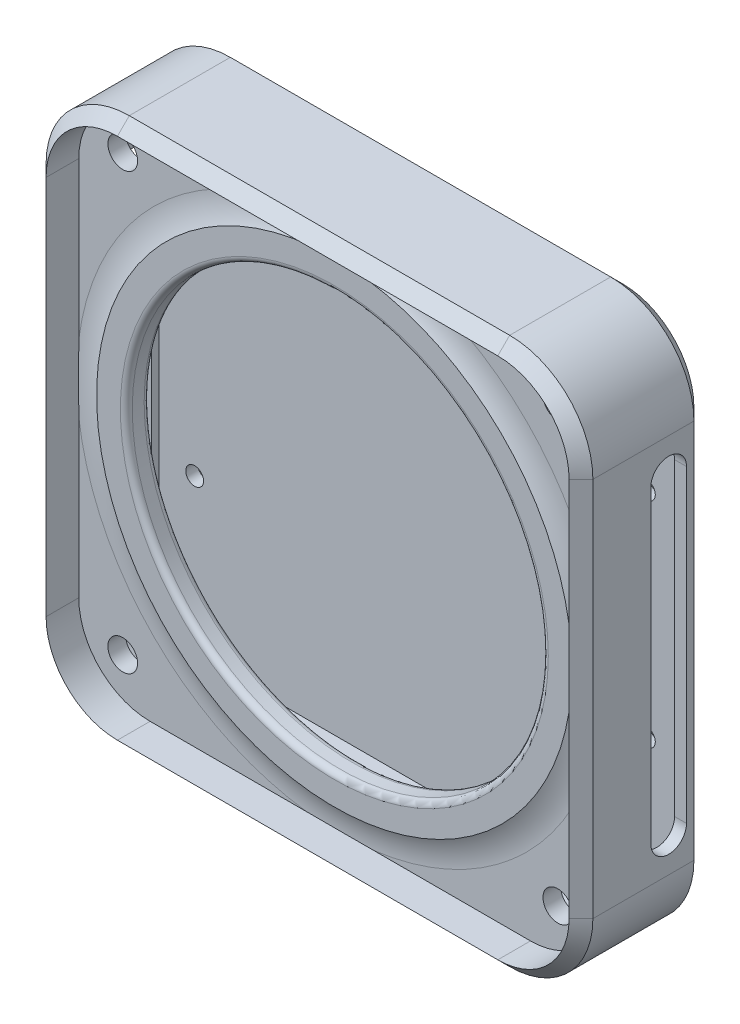
SolidWorks part; units mm, degrees
ref_plane "Alzado" through (0, 0, 0) normal (0, 0, 1) x (1, 0, 0)
ref_plane "Planta" through (0, 0, 0) normal (0, 1, 0) x (1, 0, 0)
ref_plane "Vista lateral" through (0, 0, 0) normal (1, 0, 0) x (0, 0, -1)
sketch "Croquis3" plane through (0, 0, 0) normal (0, 0, 1) x (1, 0, 0)
  line L1 (-16, 23) -> (16, 23)
  line L2 (-23, 16) -> (-23, -16)
  line L3 (-16, -23) -> (16, -23)
  line L4 (23, 16) -> (23, -16)
  line L5 (-23, 23) -> (23, -23) construction
  line L6 (-23, -23) -> (23, 23) construction
  arc A0 (16, 23) -> (23, 16) centre (16, 16) cw
  arc A1 (16, -23) -> (23, -16) centre (16, -16) ccw
  arc A2 (-23, -16) -> (-16, -23) centre (-16, -16) ccw
  arc A3 (-16, 23) -> (-23, 16) centre (-16, 16) ccw
  point P0 (0, 0)
  dimension "D3" = 7
  dimension "D1" = 46
  dimension "D2" = 46
extrude "Saliente-Extruir2" add sketch "Croquis3" along normal blind 10.5
shell "Vaciado1" thickness 1 removed face at (0, 0, 10.5)
ref_plane "Plano1" through (0, 0, 6.25) normal (0, 0, 1) x (1, 0, 0)
sketch "Croquis4" plane through (0, 0, 6.25) normal (0, 0, 1) x (1, 0, 0)
  line L1 (16, 22) -> (-16, 22) construction
  line L2 (-22, 16) -> (-22, -16) construction
  line L3 (-16, -22) -> (16, -22) construction
  line L4 (22, -16) -> (22, 16) construction
  line L5 (16, 22) -> (-16, 22)
  line L6 (-22, 16) -> (-22, -16)
  line L7 (-16, -22) -> (16, -22)
  line L8 (22, -16) -> (22, 16)
  circle A0 centre (0, 0) radius 20
  circle A1 centre (0, 0) radius 17.5
  arc A2 (-16, 22) -> (-22, 16) centre (-16, 16) ccw construction
  arc A3 (-22, -16) -> (-16, -22) centre (-16, -16) ccw construction
  arc A4 (16, -22) -> (22, -16) centre (16, -16) ccw construction
  arc A5 (22, 16) -> (16, 22) centre (16, 16) ccw construction
  arc A6 (-16, 22) -> (-22, 16) centre (-16, 16) ccw
  arc A7 (-22, -16) -> (-16, -22) centre (-16, -16) ccw
  arc A8 (16, -22) -> (22, -16) centre (16, -16) ccw
  arc A9 (22, 16) -> (16, 22) centre (16, 16) ccw
  dimension "D1" = 40
  dimension "D2" = 35
extrude "Saliente-Extruir3" add sketch "Croquis4" along normal blind 1.5 separate body contours L8 A9 L5 A6 L6 A7 L7 A8 A0 | A0 A1 region at (19.8026, 19.8026, 6.25) region at (-19.4343, 0, 6.25)
ref_plane "Plano2" through (0, 0, 7.75) normal (0, 0, 1) x (1, 0, 0)
sketch "Croquis5" plane through (0, 0, 7.75) normal (0, 0, 1) x (1, 0, 0)
  circle A0 centre (0, 0) radius 20
  circle A1 centre (0, 0) radius 17.5 construction
  circle A2 centre (0, 0) radius 17.5
  dimension "D1" = 40
extrude "Saliente-Extruir4" add sketch "Croquis5" along normal blind 0.5
fillet "Redondeo1" radius 5 1 edges at (20, 0, 7.75)
fillet "Redondeo2" radius 0.5 2 edges at (17.5, 0, 6.25) (17.5, 0, 8.25)
ref_plane "Plano3" through (-23, 0, 0) normal (-1, 0, 0) x (0, 0, 1)
sketch "Croquis6" plane through (-23, 0, 0) normal (-1, 0, 0) x (0, 0, 1)
  line L0 (0, 0) -> (6.25, 0) construction
  line L3 (0, 16) -> (0, -16) construction
  line L4 (3.125, -13) -> (3.125, 13) construction
  line L5 (1.625, -13) -> (1.625, 13)
  line L6 (4.625, -13) -> (4.625, 13)
  arc A0 (1.625, -13) -> (4.625, -13) centre (3.125, -13) ccw
  arc A1 (4.625, 13) -> (1.625, 13) centre (3.125, 13) ccw
  point P4 (3.125, 0)
  point P7 (3.125, 0)
  dimension "D1" = 6.25
  dimension "D2" = 26
  dimension "D3" = 3
extrude "Cortar-Extruir1" cut sketch "Croquis6" against normal through all
chamfer "Chaflán1" distance 1 angle 45 8 edges at (20.9497, -20.9497, 10.5) (23, 0, 10.5) (0, -23, 10.5) (20.9497, 20.9497, 10.5) (-20.9497, -20.9497, 10.5) (0, 23, 10.5) (-23, 0, 10.5) (-20.9497, 20.9497, 10.5)
chamfer "Chaflán2" distance 1 angle 45 8 edges at (20.9497, 20.9497, 0) (23, 0, 0) (0, 23, 0) (20.9497, -20.9497, 0) (-20.9497, 20.9497, 0) (0, -23, 0) (-23, 0, 0) (-20.9497, -20.9497, 0)
ref_plane "Plano4" through (0, 0, 0) normal (0, 0, -1) x (-1, 0, 0)
sketch "Croquis7" plane through (0, 0, 0) normal (0, 0, -1) x (-1, 0, 0)
  line L0 (-19, 0) -> (-19, 16) construction
  line L1 (-19, 0) -> (0, 0) construction
  line L2 (-22, 16) -> (-22, -16) construction
  line L3 (16, 22) -> (-16, 22) construction
  line L4 (0, 0) -> (0, 10.9894) construction
  circle A0 centre (-19, 9) radius 0.75
  circle A1 centre (-19, -9) radius 0.75
  circle A2 centre (19, -9) radius 0.75
  circle A3 centre (19, 9) radius 0.75
  point P6 (-19, 9)
  dimension "D3" = 1.5
  dimension "D1" = 3
  dimension "D2" = 13
extrude "Cortar-Extruir2" cut sketch "Croquis7" against normal blind 1
sketch "Croquis8" plane through (0, -23, 0) normal (0, -1, 0) x (1, 0, 0)
  line L0 (-16, 5.25) -> (16, 5.25) construction
  line L1 (-16, 9.5) -> (-16, 1) construction
  line L2 (16, 9.5) -> (16, 1) construction
  circle A0 centre (0, 5.25) radius 0.5
  dimension "D1" = 1
extrude "Cortar-Extruir3" cut sketch "Croquis8" against normal blind 10
sketch "Croquis9" plane through (0, 0, 7.75) normal (0, 0, 1) x (1, 0, 0)
  line L0 (16, 22) -> (2.8157, 22) construction
  line L1 (22, -16) -> (22, 16) construction
  line L2 (0, 0) -> (8.744, 0) construction
  line L3 (0, 0) -> (0, 7.8646) construction
  circle A0 centre (18.3, 18.3) radius 1.25
  circle A1 centre (-18.3, 18.3) radius 1.25
  circle A2 centre (-18.3, -18.3) radius 1.25
  circle A3 centre (18.3, -18.3) radius 1.25
  dimension "D3" = 2.5
  dimension "D1" = 3.7
  dimension "D2" = 3.7
extrude "Cortar-Extruir4" cut sketch "Croquis9" against normal blind 1.5
